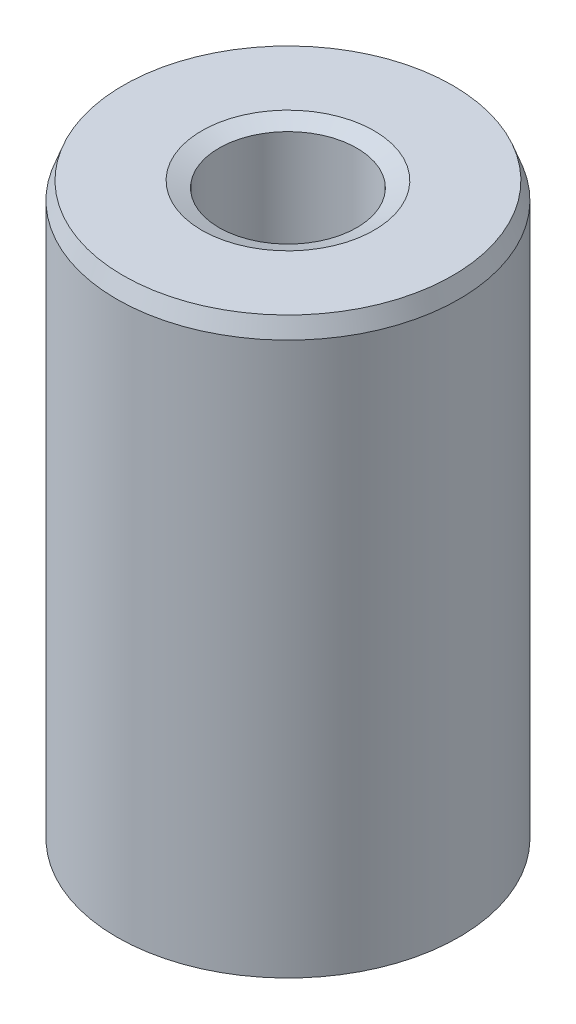
SolidWorks part; units mm, degrees
ref_plane "Front Plane" through (0, 0, 0) normal (0, 0, 1) x (1, 0, 0)
ref_plane "Top Plane" through (0, 0, 0) normal (0, 1, 0) x (1, 0, 0)
ref_plane "Right Plane" through (0, 0, 0) normal (1, 0, 0) x (0, 0, -1)
sketch "Sketch1" plane through (0, 0, 0) normal (0, 1, 0) x (1, 0, 0)
  circle A0 centre (0, 0) radius 25
  dimension "SLEEVE_OD" = 50
extrude "Boss-Extrude1" add sketch "Sketch1" along normal blind 84.1594
sketch "Sketch2" plane through (0, 0, 0) normal (0, 1, 0) x (1, 0, 0)
  circle A0 centre (0, 0) radius 10.0692
  dimension "BORE_D" = 20.1384
extrude "Cut-Extrude1" cut sketch "Sketch2" along normal through all
chamfer "Chamfer1" distance 2.5242 angle 20.247 4 edges at (0, 84.1594, 10.0692) (0, 0, 10.0692) (0, 0, 25) (0, 84.1594, 25) first distance on face at (0, 84.1594, 10.0692) first distance on face at (0, 0, 10.0692) first distance on face at (0, 84.1594, 25)
